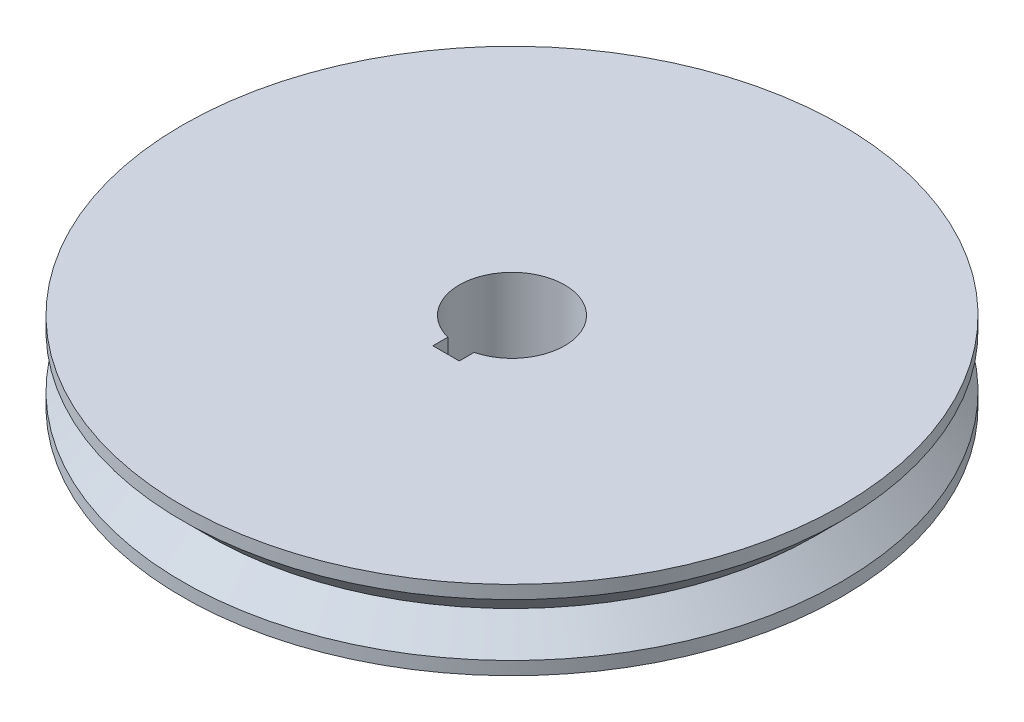
SolidWorks part; units mm, degrees
ref_plane "Front" through (0, 0, 0) normal (0, 0, 1) x (1, 0, 0)
ref_plane "Top" through (0, 0, 0) normal (0, 1, 0) x (1, 0, 0)
ref_plane "Right" through (0, 0, 0) normal (1, 0, 0) x (0, 0, -1)
sketch "Sketch1" plane through (0, 0, 0) normal (0, 0, 1) x (1, 0, 0)
  line L0 (0, 0) -> (115, 0) construction
  line L1 (0, 15) -> (125, 15)
  line L2 (0, 15) -> (0, -15)
  line L3 (0, -15) -> (125, -15)
  line L4 (125, 15) -> (125, 10)
  line L5 (115, 0) -> (125, 10)
  line L6 (115, 0) -> (125, -10)
  line L7 (125, -10) -> (125, -15)
  line L8 (0, -15) -> (0, -47.2315) construction
  dimension "D2" = 30
  dimension "D3" = 20
  dimension "OD" = 250
revolve "Revolve1" add sketch "Sketch1" angle 360 about L8
sketch "Sketch2" plane through (0, 15, 0) normal (0, 1, 0) x (-1, 0, 0)
  line L2 (-5, 19.3649) -> (-5, 25)
  line L3 (-5, 25) -> (5, 25)
  line L4 (5, 19.3649) -> (5, 25)
  arc A0 (-5, 19.3649) -> (5, 19.3649) centre (0, 0) ccw
  point P1 (0, 25)
  dimension "D1" = 40
  dimension "D2" = 25
  dimension "D3" = 10
extrude "Cut-Extrude1" cut sketch "Sketch2" against normal through all
ref_axis "Axis1" through (0, 50, 0) along (0, -1, 0)
sketch "Sketch4" [suppressed] plane through (0, 15, 0) normal (0, 1, 0) x (-1, 0, 0)
  circle A0 centre (0, 125) radius 12.5
  dimension "D2" = 25
  dimension "D1" = 125
extrude "Extrude1" [suppressed] add sketch "Sketch4" along normal blind 50
ref_axis "Axis2" [suppressed] through (0, 15, 125) along (0, 1, 0)
sketch "Sketch5" plane through (0, 15, 0) normal (0, 1, 0) x (1, 0, 0)
  line L0 (0, 0) -> (108.2532, 62.5) construction
  line L1 (0, 0) -> (-108.2532, 62.5) construction
  line L2 (0, 0) -> (0, -125) construction
  line L3 (27.4218, 44.6995) -> (54.582, 60.3805)
  line L4 (-27.4218, 44.6995) -> (-54.582, 60.3805)
  line L5 (0, 28.8675) -> (95.7532, 84.1506) construction
  line L6 (0, 28.8675) -> (-95.7532, 84.1506) construction
  circle A0 centre (0, 0) radius 125 construction
  arc A1 (-55.4152, 77.1632) -> (-54.582, 60.3805) centre (-49.582, 69.0407) ccw
  arc A2 (54.582, 60.3805) -> (55.4152, 77.1632) centre (49.582, 69.0407) ccw
  arc A3 (12.5, -48.4123) -> (-12.5, -48.4123) centre (0, 0) ccw
  arc A4 (22.6562, 44.5724) -> (-22.6562, 44.5724) centre (0, 0) ccw
  arc A5 (-22.6562, 44.5724) -> (-27.4218, 44.6995) centre (-24.9218, 49.0296) cw
  circle A6 centre (0, 0) radius 95
  arc A7 (55.4152, 77.1632) -> (-55.4152, 77.1632) centre (0, 0) ccw
  arc A8 (22.6562, 44.5724) -> (27.4218, 44.6995) centre (24.9218, 49.0296) ccw
  dimension "D5" = 10
  dimension "D6" = 5
  dimension "D1" = 120
  dimension "D2" = 25
  dimension "D3" = 30
  dimension "D4" = 30
extrude "Cut-Extrude2" [suppressed] cut sketch "Sketch5" against normal through all
pattern_circular "CirPattern1" [suppressed] count 3 over 360 about axis through (0, -15, 0) along (0, -1, 0) of bodies 106
fillet "Fillet1" [suppressed] radius 5
sketch "Sketch6" [suppressed] plane through (0, 65, 0) normal (0, 1, 0) x (1, 0, 0)
  circle A0 centre (0, -125) radius 25
  dimension "D1" = 50
extrude "Extrude2" [suppressed] add sketch "Sketch6" along normal blind 10
